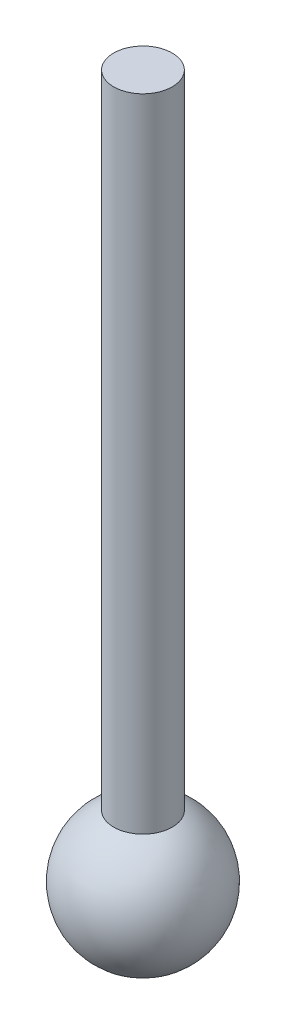
SolidWorks part; units mm, degrees
material "Plain Carbon Steel"
ref_plane "Front Plane" through (0, 0, 0) normal (0, 0, 1) x (1, 0, 0)
ref_plane "Top Plane" through (0, 0, 0) normal (0, 1, 0) x (1, 0, 0)
ref_plane "Right Plane" through (0, 0, 0) normal (1, 0, 0) x (0, 0, -1)
sketch "Sketch1" plane through (0, 0, 0) normal (0, 0, 1) x (1, 0, 0)
  line L0 (0, -7) -> (0, 72) construction
  line L1 (3, 6.3246) -> (3, 72)
  line L2 (3, 72) -> (0, 72)
  line L3 (0, 72) -> (0, -7)
  arc A0 (0, -7) -> (3, 6.3246) centre (0, 0) ccw
revolve "Revolve1" add sketch "Sketch1" angle 360 about L0
